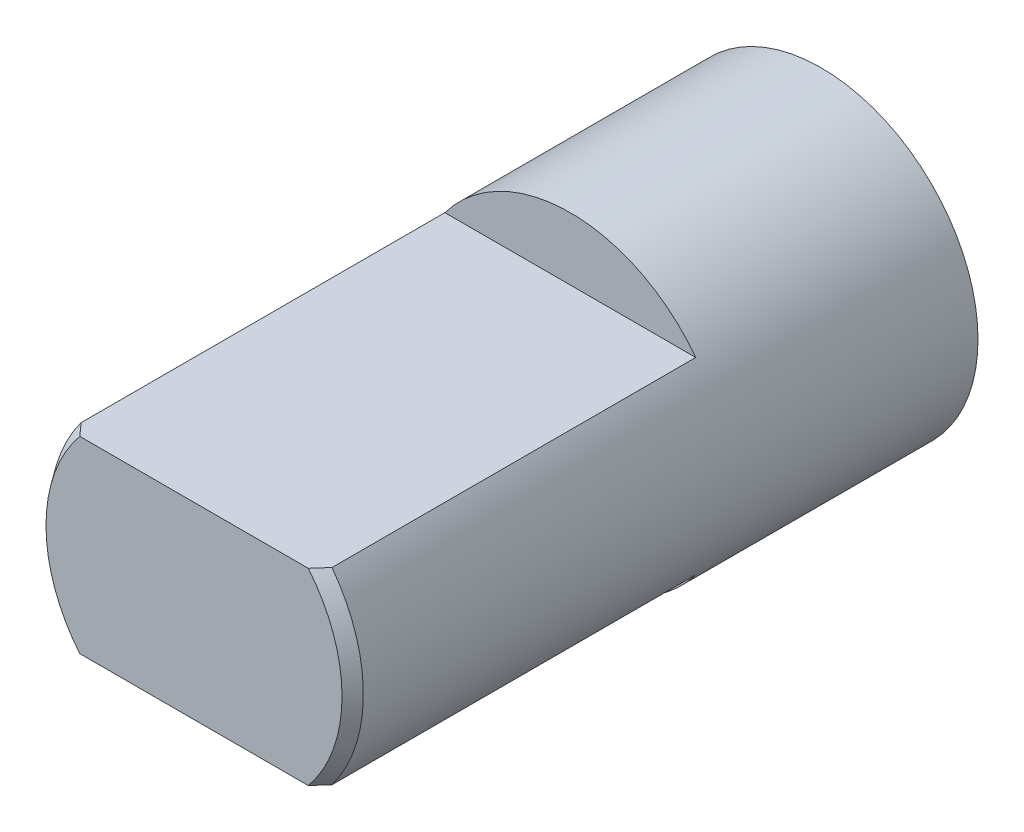
SolidWorks part; units mm, degrees
ref_plane "Front Plane" through (0, 0, 0) normal (0, 0, 1) x (1, 0, 0)
ref_plane "Top Plane" through (0, 0, 0) normal (0, 1, 0) x (1, 0, 0)
ref_plane "Right Plane" through (0, 0, 0) normal (1, 0, 0) x (0, 0, -1)
sketch "Sketch2" plane through (0, 0, 0) normal (0, 0, 1) x (1, 0, 0)
  circle A0 centre (0, 0) radius 2.5
  dimension "D1" = 5
extrude "Boss-Extrude1" add sketch "Sketch2" along normal blind 10
sketch "Sketch3" plane through (0, 0, 10) normal (0, 0, 1) x (1, 0, 0)
  line L0 (-2, 1.5) -> (2, 1.5)
  line L1 (-2.5, 0) -> (2.5, 0) construction
  line L2 (-2, -1.5) -> (2, -1.5)
  circle A0 centre (0, 0) radius 2.5 construction
  arc A1 (-2, 1.5) -> (2, 1.5) centre (0, 0) cw
  arc A2 (-2, -1.5) -> (2, -1.5) centre (0, 0) ccw
  dimension "D1" = 3
extrude "Cut-Extrude1" cut sketch "Sketch3" against normal blind 6
chamfer "Chamfer1" distance 0.2 angle 35 2 edges at (-2.5, 0, 10) (2.5, 0, 10) first distance on face at (0, 0, 7)
